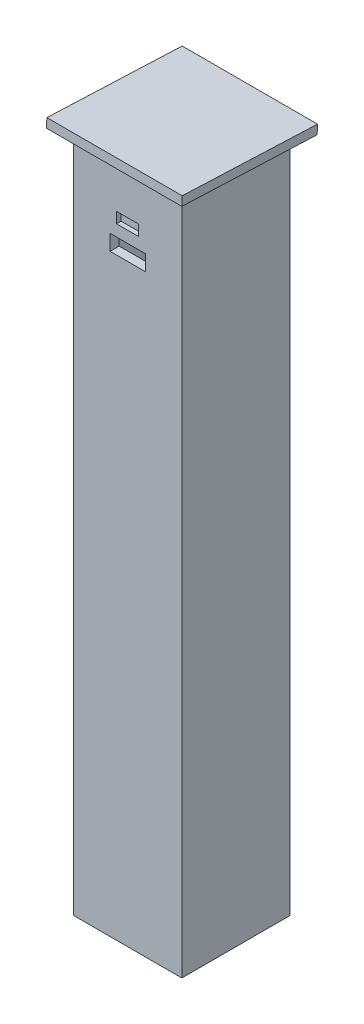
SolidWorks part; units mm, degrees
ref_plane "Спереди" through (0, 0, 0) normal (0, 0, 1) x (1, 0, 0)
ref_plane "Сверху" through (0, 0, 0) normal (0, 1, 0) x (1, 0, 0)
ref_plane "Справа" through (0, 0, 0) normal (1, 0, 0) x (0, 0, -1)
sketch "Эскиз1" plane through (0, 0, 0) normal (0, 1, 0) x (1, 0, 0)
  line L1 (-263.3228, 128.3516) -> (-63.3228, 128.3516)
  line L2 (-263.3228, 128.3516) -> (-263.3228, -71.6484)
  line L3 (-263.3228, -71.6484) -> (-63.3228, -71.6484)
  line L4 (-63.3228, 128.3516) -> (-63.3228, -71.6484)
  line L5 (-283.3228, 148.3516) -> (-43.3228, 148.3516)
  line L6 (-283.3228, 148.3516) -> (-283.3228, -91.6484)
  line L7 (-283.3228, -91.6484) -> (-43.3228, -91.6484)
  line L8 (-43.3228, 148.3516) -> (-43.3228, -91.6484)
  dimension "D1" = 200
  dimension "D2" = 200
  dimension "D3" = 20
  dimension "D4" = 20
  dimension "D5" = 20
  dimension "D6" = 20
extrude "Бобышка-Вытянуть1" add sketch "Эскиз1" along normal blind 1500
sketch "Эскиз2" plane through (0, 0, 91.6484) normal (0, 0, 1) x (1, 0, 0)
  line L0 (-163.3228, 1500) -> (-163.3228, -337.4363) construction
  line L1 (-283.3228, 1500) -> (-43.3228, 1500) construction
  line L3 (-202.3228, 1350) -> (-124.3228, 1350)
  line L4 (-202.3228, 1350) -> (-202.3228, 1315.5)
  line L5 (-202.3228, 1315.5) -> (-124.3228, 1315.5)
  line L6 (-124.3228, 1350) -> (-124.3228, 1315.5)
  point P8 (-163.3228, 1350)
  dimension "D1" = 34.5
  dimension "D2" = 78
  dimension "D3" = 150
extrude "Вырез-Вытянуть1" cut sketch "Эскиз2" against normal up to surface (20 mm away) up to face at (-163.3228, 750, 71.6484)
sketch "Эскиз3" plane through (-283.3228, 0, 0) normal (-1, 0, 0) x (0, 0, 1)
  line L0 (-148.3516, 1500) -> (91.6484, 1500)
  line L1 (91.6484, 1500) -> (91.6484, 1510)
  line L2 (91.6484, 1510) -> (-148.3516, 1500)
  dimension "D1" = 10
extrude "Бобышка-Вытянуть2" add sketch "Эскиз3" against normal up to surface (240 mm away) up to face at (-43.3228, 750, -28.3516)
sketch "Эскиз4" plane through (0, 1503.571, -62.6488) normal (0, 0.9991, -0.0416) x (1, 0, 0)
  line L0 (-43.3228, 85.7772) -> (-43.3228, -154.431) construction
  line L1 (-313.3228, 115.7772) -> (-13.3228, 115.7772)
  line L2 (-313.3228, 115.7772) -> (-313.3228, -184.431)
  line L3 (-313.3228, -184.431) -> (-13.3228, -184.431)
  line L4 (-13.3228, 115.7772) -> (-13.3228, -184.431)
  line L5 (-43.3228, -154.431) -> (-283.3228, -154.431) construction
  line L6 (-283.3228, -154.431) -> (-283.3228, 85.7772) construction
  line L7 (-43.3228, 85.7772) -> (-283.3228, 85.7772) construction
  dimension "D1" = 30
  dimension "D2" = 30
  dimension "D3" = 30
  dimension "D4" = 30
extrude "Бобышка-Вытянуть3" add sketch "Эскиз4" along normal blind 20
sketch "Эскиз5" plane through (0, 0, 91.6484) normal (0, 0, 1) x (1, 0, 0)
  line L8 (-163.3228, 1511.2489) -> (-163.3228, 1253.7199) construction
  line L9 (-187.8228, 1399.5) -> (-138.8228, 1399.5)
  line L10 (-187.8228, 1399.5) -> (-187.8228, 1375.5)
  line L11 (-187.8228, 1375.5) -> (-138.8228, 1375.5)
  line L23 (-138.8228, 1399.5) -> (-138.8228, 1375.5)
  line L24 (-313.3228, 1511.2489) -> (-13.3228, 1511.2489) construction
  line L25 (-124.3228, 1350) -> (-202.3228, 1350) construction
  point P8 (-163.3228, 1399.5)
  dimension "D2" = 24
  dimension "D3" = 25.5
  dimension "D1" = 49
sketch "Эскиз6" plane through (0, 0, 91.6484) normal (0, 0, 1) x (1, 0, 0)
  line L0 (-163.3228, 1510) -> (-163.3228, 1337.4959) construction
  line L1 (-43.3228, 1510) -> (-283.3228, 1510) construction
  line L2 (-124.3228, 1350) -> (-202.3228, 1350) construction
  line L3 (-187.8228, 1399.5) -> (-138.8228, 1399.5)
  line L4 (-187.8228, 1399.5) -> (-187.8228, 1375.5)
  line L5 (-187.8228, 1375.5) -> (-138.8228, 1375.5)
  line L6 (-138.8228, 1399.5) -> (-138.8228, 1375.5)
  point P10 (-163.3228, 1399.5)
  dimension "D1" = 49
  dimension "D2" = 24
  dimension "D3" = 25.5
extrude "Вырез-Вытянуть3" cut sketch "Эскиз6" against normal blind 10
